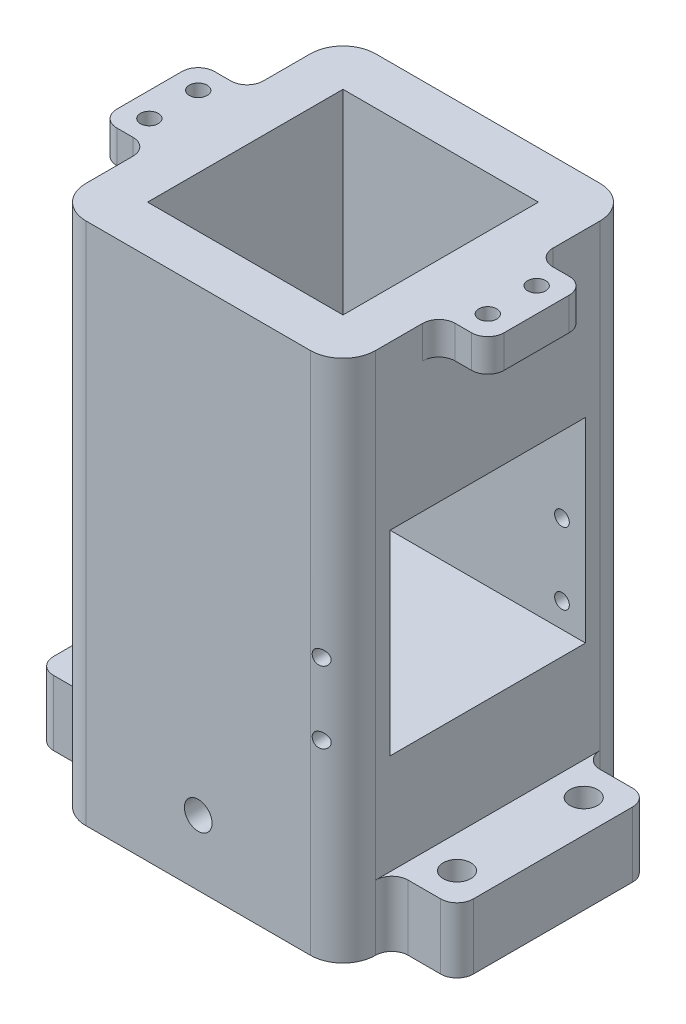
SolidWorks part; units mm, degrees
ref_plane "Front Plane" through (0, 0, 0) normal (0, 0, 1) x (1, 0, 0)
ref_plane "Top Plane" through (0, 0, 0) normal (0, 1, 0) x (1, 0, 0)
ref_plane "Right Plane" through (0, 0, 0) normal (1, 0, 0) x (0, 0, -1)
sketch "Sketch3" plane through (0, 0, 0) normal (0, 1, 0) x (1, 0, 0)
  line L1 (0, 0) -> (88.9, 0)
  line L2 (0, 0) -> (0, 88.9)
  line L3 (0, 88.9) -> (88.9, 88.9)
  line L4 (88.9, 0) -> (88.9, 88.9)
  dimension "D1" = 88.9
  dimension "D2" = 88.9
extrude "Boss-Extrude2" add sketch "Sketch3" along normal blind 50.8
ref_plane "Plane1" through (44.45, 0, 0) normal (-1, 0, 0) x (0, 0, 1)
sketch "Sketch5" plane through (0, 50.8, 0) normal (0, 1, 0) x (1, 0, 0)
  line L6 (0, 0) -> (88.9, 0)
  line L7 (0, 0) -> (0, 88.9)
  line L8 (0, 88.9) -> (88.9, 88.9)
  line L9 (88.9, 0) -> (88.9, 88.9)
sketch "Sketch7" plane through (0, 0, 0) normal (0, -1, 0) x (1, 0, 0)
  line L0 (44.45, -44.45) -> (65.45, -44.45)
  line L1 (44.45, 16.94) -> (44.45, -16.94) construction
  line L2 (65.45, -44.45) -> (65.45, -24.45)
  line L3 (65.45, -24.45) -> (23.45, -24.45)
  line L4 (23.45, -24.45) -> (23.45, -66.45)
  line L5 (23.45, -66.45) -> (65.45, -66.45)
  line L6 (65.45, -66.45) -> (65.45, -44.45)
  line L7 (44.45, -44.45) -> (44.45, -23.45)
  line L8 (44.45, -44.45) -> (44.45, -65.45)
  dimension "D1" = 21
  dimension "D3" = 42
  dimension "D4" = 42
  dimension "D5" = 21
  dimension "D6" = 21
extrude "Cut-Extrude1" cut sketch "Sketch7" against normal blind 41 contours L5 L6 L2 L3 L4 | L2 L3 L4 L5 L6 region at (41.1688, 0, -48.8875)
sketch "Sketch10" plane through (0, 0, 0) normal (-1, 0, 0) x (0, 0, 1)
  line L0 (-88.9, 0) -> (0, 0) construction
  line L1 (-73.9, 0) -> (-53.9, 0)
  line L2 (-73.9, 0) -> (-73.9, 20)
  line L3 (-73.9, 20) -> (-53.9, 20)
  line L4 (-53.9, 0) -> (-53.9, 20)
  line L5 (-88.9, 50.8) -> (-88.9, 0) construction
  line L6 (-35, 0) -> (-15, 0)
  line L7 (-35, 0) -> (-35, 20)
  line L8 (-35, 20) -> (-15, 20)
  line L9 (-15, 0) -> (-15, 20)
  dimension "D1" = 20
  dimension "D2" = 20
  dimension "D3" = 20
  dimension "D4" = 20
  dimension "D5" = 18.9
  dimension "D6" = 15
sketch "Sketch11" plane through (88.9, 0, 0) normal (1, 0, 0) x (0, 0, -1)
  line L0 (0, 0) -> (88.9, 0) construction
  line L1 (15, 0) -> (35, 0)
  line L2 (15, 0) -> (15, 20)
  line L3 (15, 20) -> (35, 20)
  line L4 (35, 0) -> (35, 20)
  line L5 (0, 50.8) -> (0, 0) construction
  line L6 (53.9, 0) -> (73.9, 0)
  line L7 (53.9, 0) -> (53.9, 20)
  line L8 (53.9, 20) -> (73.9, 20)
  line L9 (73.9, 0) -> (73.9, 20)
  line L10 (88.9, 50.8) -> (88.9, 0) construction
  dimension "D1" = 20
  dimension "D2" = 20
  dimension "D3" = 15
  dimension "D4" = 15
extrude "Boss-Extrude4" add sketch "Sketch10" along normal blind 20
extrude "Boss-Extrude5" add sketch "Sketch11" along normal blind 20
sketch "Sketch12" plane through (0, 0, 0) normal (0, -1, 0) x (1, 0, 0)
  line L0 (-20, -35) -> (-20, -15) construction
  line L1 (-20, -15) -> (0, -15) construction
  line L2 (-20, -73.9) -> (-20, -53.9) construction
  line L3 (-20, -53.9) -> (0, -53.9) construction
  line L4 (108.9, -15) -> (88.9, -15) construction
  line L5 (108.9, -15) -> (108.9, -35) construction
  line L6 (108.9, -73.9) -> (88.9, -73.9) construction
  line L7 (108.9, -53.9) -> (108.9, -73.9) construction
  circle A0 centre (-10, -25) radius 4.25
  circle A1 centre (98.9, -25) radius 4.25
  circle A2 centre (98.9, -63.9) radius 4.25
  circle A3 centre (-10, -63.9) radius 4.25
  dimension "D1" = 10
  dimension "D2" = 10
  dimension "D3" = 10
  dimension "D4" = 10
  dimension "D5" = 10
  dimension "D6" = 10
  dimension "D7" = 10
  dimension "D8" = 10
extrude "Cut-Extrude3" cut sketch "Sketch12" against normal blind 20
sketch "Sketch13" plane through (0, 0, 0) normal (0, 0, 1) x (1, 0, 0)
  line L0 (44.45, 16.94) -> (44.45, -16.94) construction
  line L1 (0, 0) -> (88.9, 0) construction
  line L2 (88.9, 50.8) -> (88.9, 0) construction
  circle A0 centre (44.45, 20) radius 4.25
  dimension "D1" = 20
  dimension "D2" = 44.45
extrude "Cut-Extrude4" cut sketch "Sketch13" against normal blind 102
sketch "Sketch28" plane through (0, 0, 0) normal (0, -1, 0) x (1, 0, 0)
  line L1 (-20, -53.9) -> (0, -53.9)
  line L2 (-20, -53.9) -> (-20, -35)
  line L3 (-20, -35) -> (0, -35)
  line L4 (0, -53.9) -> (0, -35)
  line L5 (88.9, -35) -> (108.9, -35)
  line L6 (88.9, -35) -> (88.9, -53.9)
  line L7 (88.9, -53.9) -> (108.9, -53.9)
  line L8 (108.9, -35) -> (108.9, -53.9)
extrude "Boss-Extrude7" add sketch "Sketch28" against normal blind 20
sketch "Sketch30" plane through (0, 50.8, 0) normal (0, 1, 0) x (1, 0, 0)
  line L1 (0, 0) -> (88.9, 0)
  line L2 (0, 0) -> (0, 88.9)
  line L3 (0, 88.9) -> (88.9, 88.9)
  line L4 (88.9, 0) -> (88.9, 88.9)
  line L5 (14.45, 74.45) -> (74.45, 74.45)
  line L6 (14.45, 74.45) -> (14.45, 14.45)
  line L7 (14.45, 14.45) -> (74.45, 14.45)
  line L8 (74.45, 74.45) -> (74.45, 14.45)
  dimension "D1" = 60
  dimension "D2" = 60
  dimension "D3" = 14.45
  dimension "D4" = 14.45
extrude "Boss-Extrude8" add sketch "Sketch30" along normal blind 110
sketch "Sketch31" plane through (0, 160.8, 0) normal (0, 1, 0) x (1, 0, 0)
  line L0 (0, 0) -> (0, 88.9) construction
  line L9 (0, 44.45) -> (-15, 44.45)
  line L10 (0, 44.45) -> (0, 59.45)
  line L11 (0, 59.45) -> (-15, 59.45)
  line L12 (-15, 44.45) -> (-15, 59.45)
  line L13 (88.9, 0) -> (88.9, 88.9) construction
  line L14 (0, 44.45) -> (-15, 44.45)
  line L15 (0, 44.45) -> (0, 29.45)
  line L16 (0, 29.45) -> (-15, 29.45)
  line L17 (-15, 44.45) -> (-15, 29.45)
  line L18 (88.9, 44.45) -> (103.9, 44.45)
  line L19 (88.9, 44.45) -> (88.9, 59.45)
  line L20 (88.9, 59.45) -> (103.9, 59.45)
  line L21 (103.9, 44.45) -> (103.9, 59.45)
  line L22 (0, 59.45) -> (0, 29.45)
  line L23 (88.9, 44.45) -> (103.9, 44.45)
  line L24 (88.9, 44.45) -> (88.9, 29.45)
  line L25 (88.9, 29.45) -> (103.9, 29.45)
  line L26 (103.9, 44.45) -> (103.9, 29.45)
  circle A6 centre (-7.5, 51.95) radius 2.75
  circle A7 centre (-7.5, 36.95) radius 2.75
  circle A8 centre (96.4, 51.95) radius 2.75
  circle A9 centre (96.4, 36.95) radius 2.75
  line M1 (0, 88.9) -> (0, 0)
  line M3 (88.9, 0) -> (88.9, 88.9)
  dimension "D1" = 15
  dimension "D5" = 15
  dimension "D2" = 15
  dimension "D3" = 15
  dimension "D4" = 15
  dimension "D6" = 15
  dimension "D7" = 15
  dimension "D8" = 15
extrude "Boss-Extrude10" add sketch "Sketch31" against normal blind 10 contours L12 L9 L11 A6 M1 | L9 L17 L16 A7 M1 | L18 L21 L20 A8 M3 | L26 L18 L25 A9 M3 region at (-0.2121, 160.8, -36.95) region at (-7.5, 160.8, -44.6621) region at (89.1121, 160.8, -51.95) region at (96.4, 160.8, -44.2379)
fillet "Fillet6" radius 5 16 edges at (-20, 10, -15) (0, 10, -15) (-20, 10, -73.9) (0, 10, -73.9) (108.9, 10, -73.9) (88.9, 10, -73.9) (88.9, 10, -15) (108.9, 10, -15) (103.9, 155.8, -59.45) (88.9, 155.8, -59.45) (103.9, 155.8, -29.45) (88.9, 155.8, -29.45) (-15, 155.8, -29.45) (0, 155.8, -29.45) (-15, 155.8, -59.45) (0, 155.8, -59.45)
fillet "Fillet1" radius 10 4 edges at (0, 80.4, 0) (0, 80.4, -88.9) (88.9, 80.4, -88.9) (88.9, 80.4, 0)
sketch "Sketch33" plane through (88.9, 0, 0) normal (1, 0, 0) x (0, 0, -1)
  line L1 (14.45, 50.8) -> (74.45, 50.8)
  line L2 (14.45, 50.8) -> (14.45, 110.8)
  line L3 (14.45, 110.8) -> (74.45, 110.8)
  line L4 (74.45, 50.8) -> (74.45, 110.8)
  line L8 (0, 160.8) -> (0, 0) construction
  dimension "D1" = 60
  dimension "D2" = 60
  dimension "D3" = 14.45
extrude "Cut-Extrude5" cut sketch "Sketch33" against normal blind 20
sketch "Sketch36" plane through (88.9, 0, 0) normal (1, 0, 0) x (0, 0, -1)
  line L0 (0, 160.8) -> (0, 0) construction
  point P0 (0, 80.4)
sketch "Sketch37" plane through (0, 0, 0) normal (0, 0, 1) x (1, 0, 0)
  line L0 (88.9, 160.8) -> (88.9, 0) construction
  circle A0 centre (81.675, 80.4) radius 2.25
  circle A1 centre (81.675, 58.4) radius 2.25
  point P7 (81.675, 69.7743)
  point P8 (81.675, 80.4)
  point P9 (81.675, 80.4)
  point P10 (81.675, 80.4)
  point P11 (81.675, 80.4)
  point P12 (82.2075, 89.5598)
  dimension "D1" = 7.225
  dimension "D2" = 7.225
  dimension "D3" = 22
extrude "Cut-Extrude6" cut sketch "Sketch37" against normal blind 113
